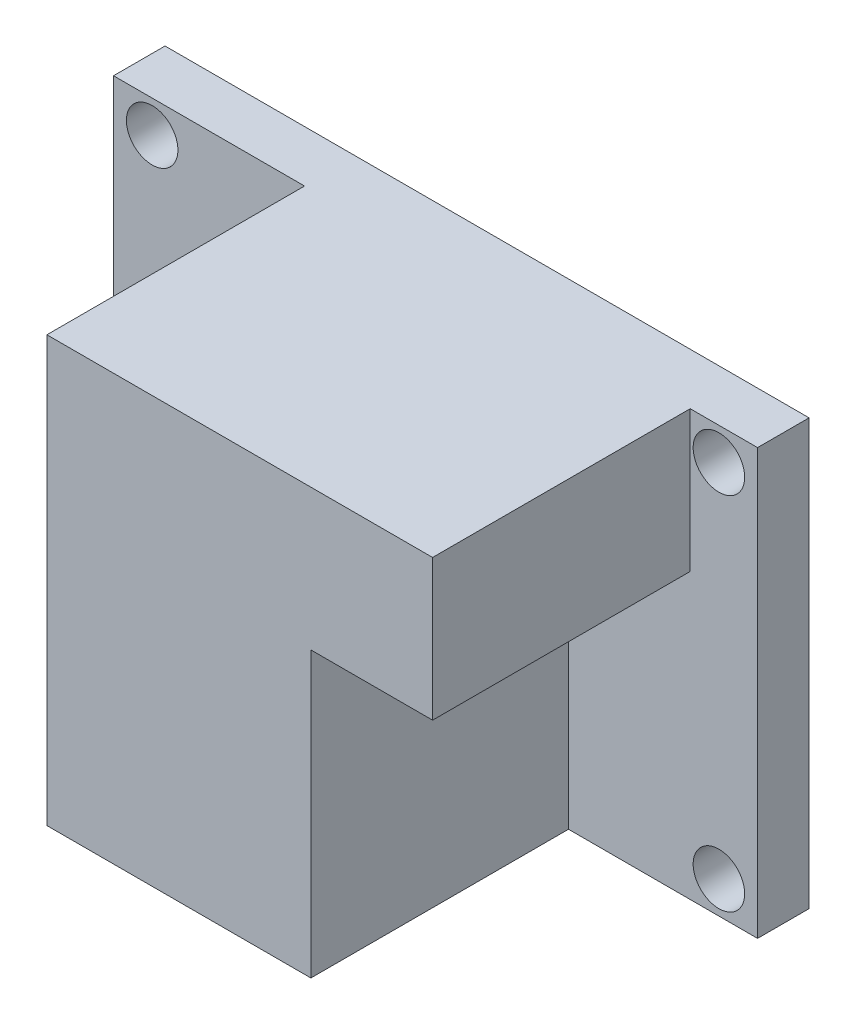
SolidWorks part; units mm, degrees
ref_plane "Front Plane" through (0, 0, 0) normal (0, 0, 1) x (1, 0, 0)
ref_plane "Top Plane" through (0, 0, 0) normal (0, 1, 0) x (1, 0, 0)
ref_plane "Right Plane" through (0, 0, 0) normal (1, 0, 0) x (0, 0, -1)
sketch "Sketch1" plane through (0, 0, 0) normal (0, 0, 1) x (1, 0, 0)
  line L1 (0, 0) -> (50, 0)
  line L2 (0, 0) -> (0, 33)
  line L4 (50, 0) -> (50, 33)
  line L10 (14.8297, 33) -> (14.8297, 0)
  line L11 (14.8297, 0) -> (35.3229, 0)
  line L12 (35.3229, 22.0585) -> (35.3229, 0)
  line L13 (35.3229, 22.0585) -> (44.7715, 22.0585)
  line L16 (44.7715, 22.0585) -> (44.7715, 33)
  line L17 (0, 33) -> (50, 33)
  circle A0 centre (3, 30.5) radius 2
  circle A2 centre (3, 2.5) radius 2
  circle A3 centre (47, 2.5) radius 2
  circle A4 centre (47, 30.5) radius 2
  dimension "D3" = 28
  dimension "D4" = 3
  dimension "D5" = 3
  dimension "D6" = 4
  dimension "D7" = 4
  dimension "D8" = 4
  dimension "D9" = 44
  dimension "D1" = 50
  dimension "D2" = 33
extrude "Boss-Extrude1" add sketch "Sketch1" along normal blind 4 contours L17 L2 L1 L10 A2 A0 | L17 L10 L1 L12 L13 L16 | L17 L16 L13 L12 L1 L4 A3 A4 region at (7.6539, 16.5, 0) region at (27.0615, 17.9625, 0) region at (43.1146, 13.2956, 0)
extrude "Boss-Extrude2" add sketch "Sketch1<3>" along normal blind 24 contours L17 L10 L1 L12 L13 L16 region at (27.0615, 17.9625, 0)
sketch "Sketch1<3>" plane through (0, 0, 0) normal (0, 0, 1) x (1, 0, 0) same geometry as "Sketch1"
